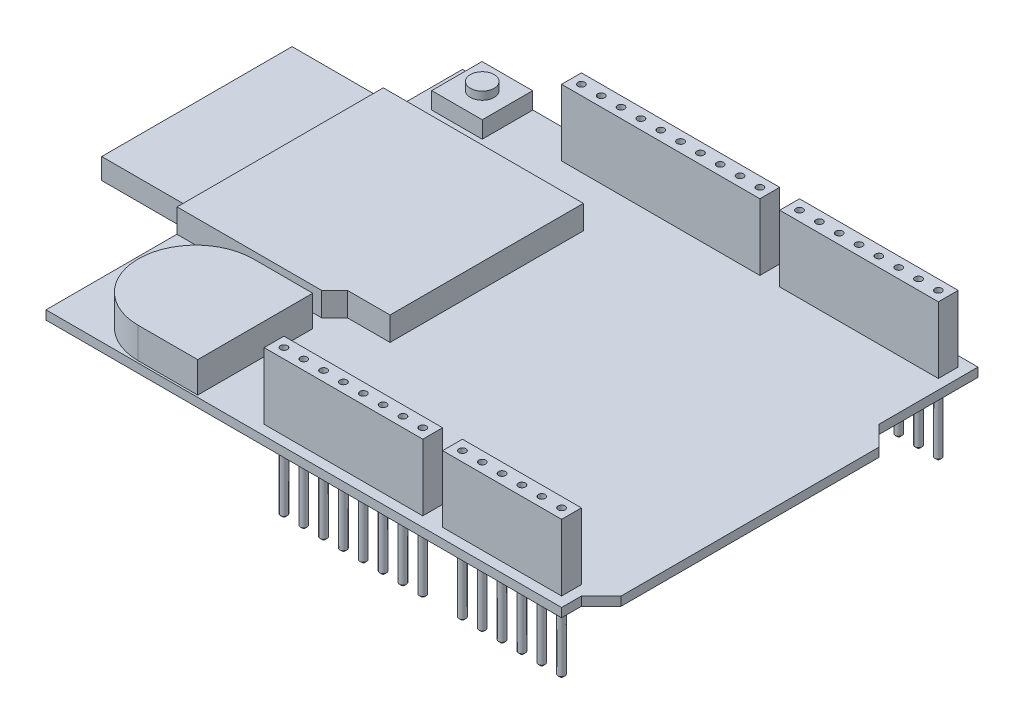
SolidWorks part; units mm, degrees
note: The reader was unsure of these and kept them because the rebuilt part matched: shared geometry of "Sketch4<3>".
ref_plane "Front Plane" through (0, 0, 0) normal (0, 0, 1) x (1, 0, 0)
ref_plane "Top Plane" through (0, 0, 0) normal (0, 1, 0) x (1, 0, 0)
ref_plane "Right Plane" through (0, 0, 0) normal (1, 0, 0) x (0, 0, -1)
sketch "Sketch3" plane through (0, 0, 0) normal (0, 1, 0) x (1, 0, 0)
  line L0 (0, 0) -> (0, 53.34)
  line L1 (0, 53.34) -> (66.04, 53.34)
  line L2 (66.04, 53.34) -> (66.04, 40.64)
  line L3 (0, 0) -> (66.04, 0)
  line L4 (66.04, 0) -> (66.04, 2.54)
  line L5 (66.04, 2.54) -> (68.58, 2.54)
  line L6 (68.58, 2.54) -> (68.58, 5.08)
  line L7 (66.04, 40.64) -> (66.04, 38.1)
  line L8 (66.04, 38.1) -> (68.58, 38.1)
  line L9 (66.04, 40.64) -> (68.58, 38.1)
  line L10 (68.58, 38.1) -> (68.58, 5.08)
  line L11 (68.58, 5.08) -> (66.04, 2.54)
  dimension "D1" = 53.34
  dimension "D2" = 66.04
  dimension "D3" = 12.7
  dimension "D4" = 66.04
  dimension "D5" = 2.54
  dimension "D6" = 2.54
  dimension "D7" = 2.54
  dimension "D8" = 2.54
  dimension "D9" = 2.54
extrude "Boss-Extrude1" add sketch "Sketch3" along normal blind 1.143 contours L11 L10 L8 L7 L2 L1 L0 L3 L4 | L9 L7 L8
sketch "Sketch4" plane through (0, 1.143, 0) normal (0, 1, 0) x (1, 0, 0)
  line L0 (66.04, 0) -> (63.5, 0)
  line L1 (0, 0) -> (66.04, 0) construction
  line L2 (63.5, 0) -> (63.5, 2.54)
  line L3 (63.5, 2.54) -> (58.697, 2.54)
  line L4 (50.8, 2.54) -> (45.72, 2.54)
  line L5 (45.72, 50.8) -> (40.64, 50.8)
  line L6 (66.04, 53.34) -> (63.5, 53.34)
  line L7 (66.04, 53.34) -> (66.04, 50.8)
  line L8 (66.04, 50.8) -> (63.5, 50.8)
  line L9 (63.5, 53.34) -> (63.5, 50.8)
  line L10 (64.77, 50.8) -> (64.77, 53.34) construction
  line L11 (66.04, 52.07) -> (63.5, 52.07) construction
  line L13 (64.77, 52.07) -> (44.45, 52.07)
  line L14 (64.77, 52.07) -> (64.77, 49.53)
  line L15 (64.77, 49.53) -> (44.45, 49.53)
  line L16 (44.45, 52.07) -> (44.45, 49.53)
  line L17 (54.61, 49.53) -> (54.61, 52.07) construction
  line L18 (64.77, 50.8) -> (44.45, 50.8) construction
  line L19 (40.64, 50.8) -> (41.91, 50.8)
  line L20 (40.64, 50.8) -> (40.64, 52.07)
  line L21 (40.64, 52.07) -> (41.91, 52.07)
  line L22 (41.91, 50.8) -> (41.91, 52.07)
  line L23 (41.275, 52.07) -> (41.275, 50.8) construction
  line L24 (40.64, 51.435) -> (41.91, 51.435) construction
  line L25 (41.91, 52.07) -> (16.51, 52.07)
  line L26 (41.91, 52.07) -> (41.91, 49.53)
  line L27 (41.91, 49.53) -> (16.51, 49.53)
  line L28 (16.51, 52.07) -> (16.51, 49.53)
  line L29 (29.21, 49.53) -> (29.21, 52.07) construction
  line L30 (41.91, 50.8) -> (16.51, 50.8) construction
  line L31 (63.5, 2.54) -> (64.77, 2.54)
  line L32 (63.5, 2.54) -> (63.5, 1.27)
  line L33 (63.5, 1.27) -> (64.77, 1.27)
  line L34 (64.77, 2.54) -> (64.77, 1.27)
  line L35 (64.135, 1.27) -> (64.135, 2.54) construction
  line L36 (63.5, 1.905) -> (64.77, 1.905) construction
  line L37 (64.77, 1.27) -> (49.53, 1.27)
  line L38 (64.77, 1.27) -> (64.77, 3.81)
  line L39 (64.77, 3.81) -> (49.53, 3.81)
  line L40 (49.53, 1.27) -> (49.53, 3.81)
  line L41 (57.15, 3.81) -> (57.15, 1.27) construction
  line L42 (64.77, 2.54) -> (49.53, 2.54) construction
  line L43 (45.72, 2.54) -> (46.99, 2.54)
  line L44 (45.72, 2.54) -> (45.72, 1.27)
  line L45 (45.72, 1.27) -> (46.99, 1.27)
  line L46 (46.99, 2.54) -> (46.99, 1.27)
  line L47 (46.355, 1.27) -> (46.355, 2.54) construction
  line L48 (45.72, 1.905) -> (46.99, 1.905) construction
  line L49 (46.99, 1.27) -> (26.67, 1.27)
  line L50 (46.99, 1.27) -> (46.99, 3.81)
  line L51 (46.99, 3.81) -> (26.67, 3.81)
  line L52 (26.67, 1.27) -> (26.67, 3.81)
  line L53 (36.83, 3.81) -> (36.83, 1.27) construction
  line L54 (46.99, 2.54) -> (26.67, 2.54) construction
  circle A0 centre (63.5, 2.54) radius 0.4445
  circle A1 centre (60.96, 2.54) radius 0.4445
  circle A2 centre (58.42, 2.54) radius 0.4445
  circle A3 centre (55.88, 2.54) radius 0.4445
  circle A4 centre (53.34, 2.54) radius 0.4445
  circle A5 centre (50.8, 2.54) radius 0.4445
  circle A6 centre (45.72, 2.54) radius 0.4445
  circle A7 centre (43.18, 2.54) radius 0.4445
  circle A8 centre (40.64, 2.54) radius 0.4445
  circle A9 centre (38.1, 2.54) radius 0.4445
  circle A10 centre (35.56, 2.54) radius 0.4445
  circle A11 centre (33.02, 2.54) radius 0.4445
  circle A12 centre (30.48, 2.54) radius 0.4445
  circle A13 centre (27.94, 2.54) radius 0.4445
  circle A14 centre (63.5, 50.8) radius 0.4445
  circle A15 centre (60.96, 50.8) radius 0.4445
  circle A16 centre (58.42, 50.8) radius 0.4445
  circle A17 centre (55.88, 50.8) radius 0.4445
  circle A18 centre (53.34, 50.8) radius 0.4445
  circle A19 centre (50.8, 50.8) radius 0.4445
  circle A20 centre (48.26, 50.8) radius 0.4445
  circle A21 centre (45.72, 50.8) radius 0.4445
  circle A22 centre (40.64, 50.8) radius 0.4445
  circle A23 centre (38.1, 50.8) radius 0.4445
  circle A24 centre (35.56, 50.8) radius 0.4445
  circle A25 centre (33.02, 50.8) radius 0.4445
  circle A26 centre (30.48, 50.8) radius 0.4445
  circle A27 centre (27.94, 50.8) radius 0.4445
  circle A28 centre (25.4, 50.8) radius 0.4445
  circle A29 centre (22.86, 50.8) radius 0.4445
  circle A30 centre (20.32, 50.8) radius 0.4445
  circle A31 centre (17.78, 50.8) radius 0.4445
  point P86 (64.77, 52.07)
  point P111 (0, 0)
  point P114 (0, 0)
  point P115 (0, 0)
  point P126 (64.135, 1.905)
  point P137 (41.275, 51.435)
  point P150 (46.355, 1.905)
  point P219 (54.61, 50.8)
  point P305 (36.83, 2.54)
  point P380 (57.15, 2.54)
  point P383 (29.21, 50.8)
  dimension "D3" = 0.889
  dimension "D6" = 0.889
  dimension "D9" = 0.889
  dimension "D12" = 0.889
  dimension "D1" = 2.54
  dimension "D2" = 2.54
  dimension "D4" = 6
  dimension "D5" = 5.08
  dimension "D8" = 2.54
  dimension "D11" = 5.08
  dimension "D14" = 2.54
  dimension "D15" = 1.27
  dimension "D16" = 2.54
  dimension "D17" = 25.4
  dimension "D18" = 1.27
  dimension "D19" = 2.54
  dimension "D20" = 15.24
  dimension "D21" = 1.27
  dimension "D22" = 2.54
  dimension "D23" = 20.32
  dimension "D7" = 8
  dimension "D10" = 8
  dimension "D13" = 10
extrude "Boss-Extrude2" add sketch "Sketch4" against normal blind 10.16
extrude "Boss-Extrude3" add sketch "Sketch4<3>" along normal blind 8.509
sketch "Sketch4<3>" plane through (0, 1.143, 0) normal (0, 1, 0) x (1, 0, 0) same geometry as "Sketch4"
sketch "Sketch5" plane through (0, 1.143, 0) normal (0, 1, 0) x (1, 0, 0)
  line L0 (0, 0) -> (0, 16.764)
  line L1 (0, 0) -> (0, 53.34) construction
  line L2 (0, 16.764) -> (18.542, 16.764)
  line L3 (18.542, 16.764) -> (18.542, 18.415)
  line L4 (18.542, 18.415) -> (20.193, 18.415)
  line L5 (20.193, 18.415) -> (18.542, 16.764)
  line L6 (0, 16.764) -> (0, 43.18)
  line L7 (0, 43.18) -> (25.654, 43.18)
  line L8 (25.654, 43.18) -> (25.654, 18.415)
  line L9 (25.654, 18.415) -> (20.193, 18.415)
  line M17 (0, 53.34) -> (0, 0)
  dimension "D1" = 16.764
  dimension "D2" = 18.542
  dimension "D3" = 1.651
  dimension "D4" = 1.651
  dimension "D5" = 26.416
  dimension "D6" = 25.654
extrude "Boss-Extrude4" add sketch "Sketch5" along normal blind 3.048 contours L9 L8 L7 L2 L3 L4 M17 | L5 L4 L3
sketch "Sketch6" plane through (0, 0, 0) normal (-1, 0, 0) x (0, 0, 1)
  line L0 (-43.18, 1.143) -> (-16.764, 1.143)
  line L9 (-53.34, 0) -> (0, 0)
  line L10 (0, 0) -> (0, 1.143)
  line L11 (0, 1.143) -> (-16.764, 1.143)
  line L12 (-16.764, 1.143) -> (-16.764, 4.191)
  line L13 (-16.764, 4.191) -> (-43.18, 4.191)
  line L14 (-43.18, 4.191) -> (-43.18, 1.143)
  line L15 (-43.18, 1.143) -> (-53.34, 1.143)
  line L16 (-53.34, 1.143) -> (-53.34, 0)
  line L17 (-53.34, 0) -> (0, 0)
  line L18 (0, 0) -> (0, 1.143)
  line L19 (0, 1.143) -> (-16.764, 1.143)
  line L23 (-43.18, 1.143) -> (-53.34, 1.143)
  line L24 (-53.34, 1.143) -> (-53.34, 0)
  line M12 (-16.764, 1.143) -> (-16.764, 4.191)
  line M13 (-16.764, 4.191) -> (-43.18, 4.191)
  line M14 (-43.18, 4.191) -> (-43.18, 1.143)
  dimension "D1" = 0
extrude "Cut-Extrude1" cut sketch "Sketch6" against normal blind 0.0254 contours L0 M14 M12 M13
sketch "Sketch7" plane through (0.0254, 0, 0) normal (-1, 0, 0) x (0, 0, 1)
  line L0 (-16.764, 1.143) -> (-17.78, 1.143)
  line L1 (-43.18, 1.143) -> (-16.764, 1.143) construction
  line L2 (-17.8853, 4.191) -> (-17.8853, 3.937)
  line L3 (-16.764, 4.191) -> (-43.18, 4.191) construction
  line L4 (-17.78, 1.143) -> (-17.78, 1.27)
  line L6 (-43.18, 1.143) -> (-42.164, 1.143)
  line L7 (-43.18, 1.143) -> (-43.18, 1.27)
  line L8 (-43.18, 1.27) -> (-42.164, 1.27)
  line L9 (-42.164, 1.143) -> (-42.164, 1.27)
  line L10 (-42.672, 1.27) -> (-42.672, 1.143) construction
  line L11 (-43.18, 1.2065) -> (-42.164, 1.2065) construction
  line L12 (-42.164, 1.27) -> (-17.78, 1.27)
  line L13 (-42.164, 1.27) -> (-42.164, 3.937)
  line L14 (-42.164, 3.937) -> (-17.78, 3.937)
  line L15 (-17.78, 1.27) -> (-17.78, 3.937)
  line L16 (-29.972, 3.937) -> (-29.972, 1.27) construction
  line L17 (-42.164, 2.6035) -> (-17.78, 2.6035) construction
  point P58 (-42.672, 1.2065)
  point P395 (-29.972, 2.6035)
  dimension "D1" = 1.016
  dimension "D2" = 0.254
  dimension "D3" = 0.127
  dimension "D4" = 0.127
  dimension "D5" = 1.016
extrude "Boss-Extrude6" add sketch "Sketch7" along normal blind 10.668 contours L12 L15 L14 L13
sketch "Sketch8" plane through (0, 1.143, 0) normal (0, 1, 0) x (1, 0, 0)
  line L0 (0, 53.34) -> (2.54, 53.34)
  line L1 (0, 53.34) -> (66.04, 53.34) construction
  line L3 (2.54, 53.34) -> (9.017, 53.34)
  line L4 (2.54, 53.34) -> (2.54, 46.863)
  line L5 (2.54, 46.863) -> (9.017, 46.863)
  line L6 (9.017, 53.34) -> (9.017, 46.863)
  line L7 (5.7785, 46.863) -> (5.7785, 53.34) construction
  line L8 (2.54, 50.1015) -> (9.017, 50.1015) construction
  point P64 (5.7785, 50.1015)
  line M7 (66.04, 53.34) -> (0, 53.34)
  dimension "D1" = 2.54
  dimension "D2" = 6.477
extrude "Boss-Extrude7" add sketch "Sketch8" along normal blind 2.159 contours L6 L4 L5 M7
sketch "Sketch9" plane through (0, 3.302, 0) normal (0, 1, 0) x (1, 0, 0)
  line L0 (9.017, 53.34) -> (9.017, 46.863) construction
  line L1 (2.54, 53.34) -> (9.017, 53.34)
  line L2 (2.54, 53.34) -> (2.54, 46.863)
  line L3 (2.54, 46.863) -> (9.017, 46.863)
  line L4 (9.017, 53.34) -> (9.017, 46.863)
  line L5 (5.7785, 46.863) -> (5.7785, 53.34) construction
  line L6 (2.54, 50.1015) -> (9.017, 50.1015) construction
  circle A0 centre (5.7785, 50.1015) radius 1.524
  point P112 (5.7785, 50.1015)
  dimension "D1" = 3.048
extrude "Boss-Extrude9" add sketch "Sketch9" along normal blind 1.016 contours A0
sketch "Sketch10" plane through (0, 1.143, 0) normal (0, 1, 0) x (1, 0, 0)
  line L0 (0, 0) -> (4.191, 0)
  line L1 (0, 0) -> (66.04, 0) construction
  line L2 (4.191, 0) -> (4.191, 7.62)
  line L3 (4.191, 7.62) -> (11.557, 7.62)
  line L4 (11.557, 14.986) -> (19.177, 14.986)
  line L5 (19.177, 14.986) -> (19.177, 0.254)
  line L6 (19.177, 0.254) -> (11.557, 0.254)
  circle A0 centre (11.557, 7.62) radius 7.366
  dimension "D4" = 14.732
  dimension "D1" = 4.191
  dimension "D2" = 7.62
  dimension "D3" = 7.366
  dimension "D5" = 7.62
extrude "Boss-Extrude10" add sketch "Sketch10" along normal blind 3.937
sketch "Sketch11" plane through (0, 0, -53.34) normal (0, 0, -1) x (-1, 0, 0)
  line L0 (-2.54, 1.143) -> (-9.017, 1.143)
  line M5 (-2.54, 1.143) -> (-2.54, 3.302)
  line M6 (-2.54, 3.302) -> (-9.017, 3.302)
  line M7 (-9.017, 3.302) -> (-9.017, 1.143)
extrude "Cut-Extrude2" cut sketch "Sketch11" against normal blind 0.0254 and the other way through all contours L0 M5 M6 M7
chamfer "Chamfer1" distance 0.254 angle 45 64 edges at (30.48, 0, -50.3555) (30.48, -9.017, -50.3555) (33.02, 0, -50.3555) (33.02, -9.017, -50.3555) (35.56, 0, -50.3555) (35.56, -9.017, -50.3555) (38.1, 0, -50.3555) (38.1, -9.017, -50.3555) (40.64, 0, -50.3555) (40.64, -9.017, -50.3555) (45.72, 0, -50.3555) (45.72, -9.017, -50.3555) (48.26, 0, -50.3555) (48.26, -9.017, -50.3555) (50.8, 0, -50.3555) (50.8, -9.017, -50.3555) (53.34, 0, -50.3555) (53.34, -9.017, -50.3555) (55.88, 0, -50.3555) (55.88, -9.017, -50.3555) (58.42, 0, -50.3555) (58.42, -9.017, -50.3555) (60.96, 0, -50.3555) (60.96, -9.017, -50.3555) (63.5, 0, -50.3555) (63.5, -9.017, -50.3555) (27.94, 0, -50.3555) (27.94, -9.017, -50.3555) (25.4, 0, -50.3555) (25.4, -9.017, -50.3555) (22.86, 0, -50.3555) (22.86, -9.017, -50.3555) (20.32, 0, -50.3555) (20.32, -9.017, -50.3555) (17.78, 0, -50.3555) (17.78, -9.017, -50.3555) (27.94, 0, -2.0955) (27.94, -9.017, -2.0955) (30.48, 0, -2.0955) (30.48, -9.017, -2.0955) (33.02, 0, -2.0955) (33.02, -9.017, -2.0955) (35.56, 0, -2.0955) (35.56, -9.017, -2.0955) (38.1, 0, -2.0955) (38.1, -9.017, -2.0955) (40.64, 0, -2.0955) (40.64, -9.017, -2.0955) (43.18, 0, -2.0955) (43.18, -9.017, -2.0955) (45.72, 0, -2.0955) (45.72, -9.017, -2.0955) (50.8, 0, -2.0955) (50.8, -9.017, -2.0955) (53.34, 0, -2.0955) (53.34, -9.017, -2.0955) (55.88, 0, -2.0955) (55.88, -9.017, -2.0955) (58.42, 0, -2.0955) (58.42, -9.017, -2.0955) (60.96, 0, -2.0955) (60.96, -9.017, -2.0955) (63.5, 0, -2.0955) (63.5, -9.017, -2.0955)
